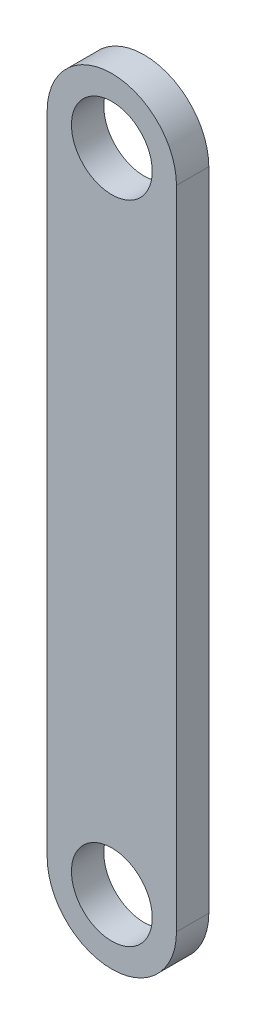
SolidWorks part; units mm, degrees
ref_plane "Front Plane" through (0, 0, 0) normal (0, 0, 1) x (1, 0, 0)
ref_plane "Top Plane" through (0, 0, 0) normal (0, 1, 0) x (1, 0, 0)
ref_plane "Right Plane" through (0, 0, 0) normal (1, 0, 0) x (0, 0, -1)
sketch "Sketch1" plane through (0, 0, 0) normal (0, 0, 1) x (1, 0, 0)
  line L0 (-5.08, 0) -> (-5.08, -50.8)
  line L1 (5.08, 0) -> (5.08, -50.8)
  arc A0 (5.08, 0) -> (-5.08, 0) centre (0, 0) ccw
  arc A1 (5.08, -50.8) -> (-5.08, -50.8) centre (0, -50.8) cw
  circle A2 centre (0, 0) radius 3.175
  circle A3 centre (0, -50.8) radius 3.175
  point P7 (0, 0)
  point P10 (0, 0)
  dimension "D3" = 5.08
  dimension "D4" = 6.35
  dimension "D5" = 6.35
  dimension "D6" = 5.08
  dimension "D2" = 50.8
extrude "Boss-Extrude1" add sketch "Sketch1" along normal blind 2.54
